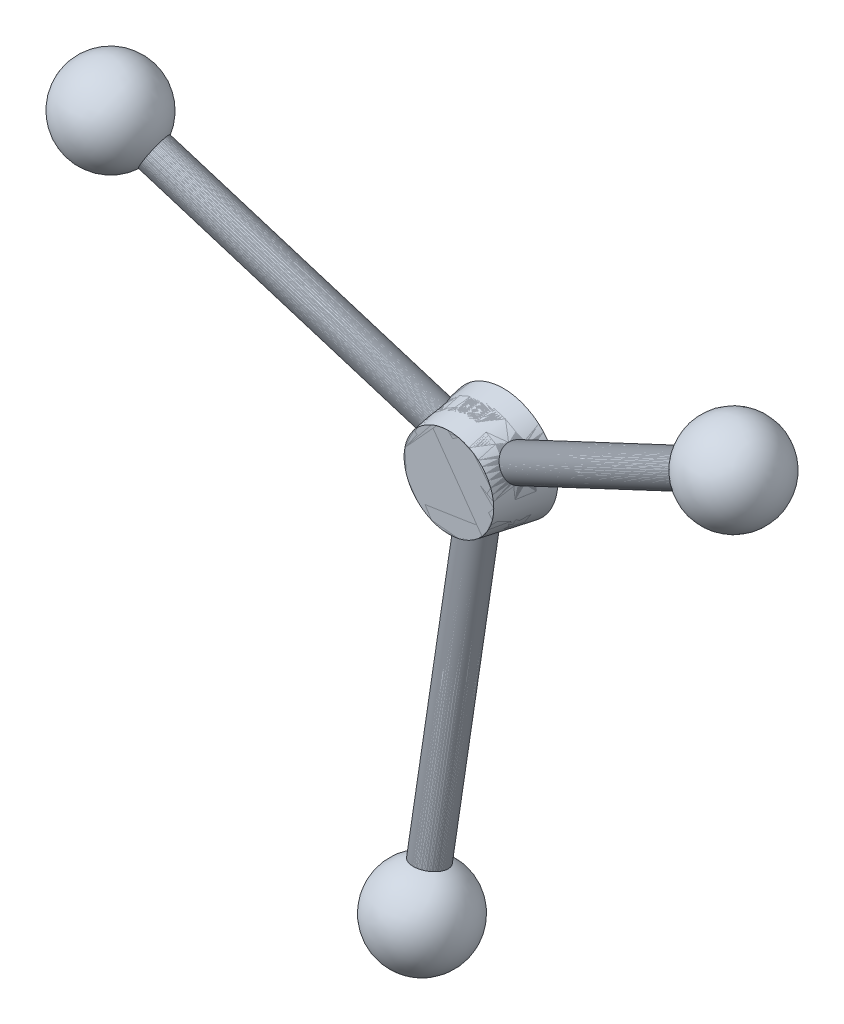
SolidWorks part; units mm, degrees
ref_plane "Front Plane" through (0, 0, 0) normal (0, 0, 1) x (1, 0, 0)
ref_plane "Top Plane" through (0, 0, 0) normal (0, 1, 0) x (1, 0, 0)
ref_plane "Right Plane" through (0, 0, 0) normal (1, 0, 0) x (0, 0, -1)
sketch "Sketch1" plane through (0, 0, 0) normal (0, 0, 1) x (1, 0, 0)
  circle A0 centre (0, 0) radius 10
  dimension "D1" = 20
extrude "Boss-Extrude1" add sketch "Sketch1" along normal blind 10 draft 10
ref_plane "Plane2" through (0, -9.6985, 1.7101) normal (0, -0.9848, 0.1736) x (-1, 0, 0)
ref_plane "Plane3" through (0, -14.6225, 2.5783) normal (0, -0.9848, 0.1736) x (-1, 0, 0)
sketch "Sketch7" plane through (0, -14.6225, 2.5783) normal (0, -0.9848, 0.1736) x (-1, 0, 0)
  line L0 (0, 0) -> (0, -9.8481) construction
  circle A0 centre (0, -3.246) radius 3
  dimension "D1" = 6
extrude "Boss-Extrude2" add sketch "Sketch7" against normal up to next and the other way blind 45
pattern_circular "CirPattern2" count 3 over 360 about axis through (0, 0, 0) along (0, 0, 1) of "Boss-Extrude2"
sketch "Sketch9" plane through (0, 0, 0) normal (1, 0, 0) x (0, 0, -1)
  line L1 (-13.5892, -58.3752) -> (-17.4565, -80.3077) construction
  line L2 (-16.5436, -57.8542) -> (-10.6348, -58.8961) construction
  line L3 (-13.5892, -58.3752) -> (-4.8559, -8.8458) construction
  line L4 (-16.4105, -74.3752) -> (-13.5892, -58.3752)
  line L5 (-13.5892, -58.3752) -> (-16.5436, -57.8542)
  arc A0 (-16.5436, -57.8542) -> (-16.4105, -74.3752) centre (-14.9517, -66.1024) ccw
  point P1 (0, 0)
  dimension "D3" = 16
sketch "Sketch10" plane through (0, 0, 0) normal (0, 0, -1) x (-1, 0, 0)
  circle A0 centre (0, 0) radius 2.5
  dimension "D1" = 5
extrude "Cut-Extrude1" cut sketch "Sketch10" against normal blind 5
revolve "Revolve1" add sketch "Sketch9" angle 360 about L1
pattern_circular "CirPattern3" count 3 every 120 about axis through (0, 0, 0) along (0, 0, -1) of "Revolve1"
